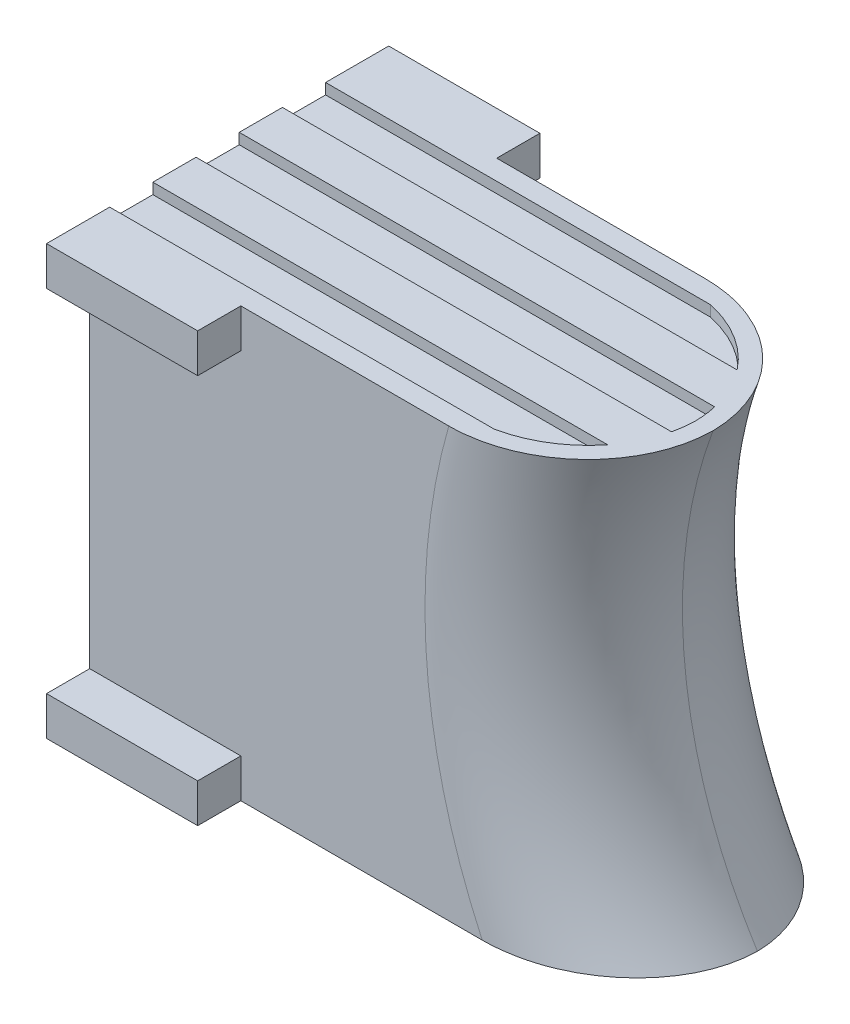
SolidWorks part; units mm, degrees
ref_plane "Front Plane" through (0, 0, 0) normal (0, 0, 1) x (1, 0, 0)
ref_plane "Top Plane" through (0, 0, 0) normal (0, 1, 0) x (1, 0, 0)
ref_plane "Right Plane" through (0, 0, 0) normal (1, 0, 0) x (0, 0, -1)
sketch "Sketch1" plane through (0, 0, 0) normal (0, 0, 1) x (1, 0, 0)
  line L1 (-40, 25.4581) -> (-17.0565, 25.4581)
  line L2 (-40, 25.4581) -> (-40, 5.6081)
  line L3 (-40, 5.6081) -> (-15, 5.6081)
  arc A0 (-17.0565, 25.4581) -> (-15, 5.6081) centre (4, 17.6081) ccw
  dimension "D1" = 19.85
  dimension "D2" = 25
  dimension "D3" = 12
  dimension "D4" = 44
extrude "Boss-Extrude1" add sketch "Sketch1" along normal blind 11.85 contours L1 A0 L3 L2
sketch "Sketch2" plane through (0, 0, 0) normal (0, 0, -1) x (-1, 0, 0)
  line L1 (40, 5.6081) -> (33, 5.6081)
  line L2 (40, 5.6081) -> (40, 7.4081)
  line L3 (40, 7.4081) -> (33, 7.4081)
  line L4 (33, 5.6081) -> (33, 7.4081)
  line L5 (40, 25.4581) -> (33, 25.4581)
  line L6 (40, 25.4581) -> (40, 23.6581)
  line L7 (40, 23.6581) -> (33, 23.6581)
  line L8 (33, 25.4581) -> (33, 23.6581)
  dimension "D1" = 1.8
  dimension "D2" = 7
  dimension "D3" = 1.8
  dimension "D4" = 7
extrude "Boss-Extrude2" add sketch "Sketch2" along normal blind 2 and the other way offset from surface (13.85 mm away) 2 other way up to face at (-28.5952, 15.4729, 11.85)
fillet "Fillet1" radius 6 2 edges at (-18.3526, 15.2923, 0) (-18.3526, 15.2923, 11.85)
sketch "Sketch3" plane through (0, 25.4581, 0) normal (0, 1, 0) x (1, 0, 0)
  line L0 (-40, -13.85) -> (-40, 2) construction
  line L1 (-40, -0.925) -> (-22.1802, -0.925)
  line L2 (-40, -0.925) -> (-40, -2.925)
  line L3 (-40, -2.925) -> (-18.9375, -2.925)
  line L5 (-17.057, -5.925) -> (-46.6866, -5.925) construction
  line L6 (-40, -4.925) -> (-17.9776, -4.925)
  line L7 (-40, -4.925) -> (-40, -6.925)
  line L8 (-40, -6.925) -> (-17.9776, -6.925)
  line L10 (-40, -8.925) -> (-18.9375, -8.925)
  line L11 (-40, -8.925) -> (-40, -10.925)
  line L12 (-40, -10.925) -> (-22.1801, -10.925)
  spline S1 degree 3 poles (-17.9776, -6.925) (-17.9031, -6.5976) (-17.8624, -6.2618) (-17.8571, -5.925) knots 0.878101 0.878101 0.878101 0.878101 1 1 1 1
  spline S2 degree 3 poles (-18.9375, -2.925) (-19.0132, -2.8285) (-19.0925, -2.7343) (-19.2907, -2.5147) (-19.4128, -2.392) (-19.7965, -2.0412) (-20.0767, -1.8299) (-20.6743, -1.4619) (-20.9869, -1.3077) (-21.5913, -1.075) (-21.8839, -0.988) (-22.1802, -0.925) knots 0.393522 0.393522 0.393522 0.393522 0.4375 0.4375 0.5 0.5 0.625 0.625 0.75 0.75 0.857745 0.857745 0.857745 0.857745
  spline S5 degree 3 poles (-4115.5954, 2851.8558) (-146.3035, 359.9865) (-60.4321, -18.0233) (-22.1543, -10.9222) (-21.9847, -10.8827) (-21.6475, -10.7876) (-21.4793, -10.7318) (-20.988, -10.543) (-20.6758, -10.3887) (-20.231, -10.1152) (-20.0871, -10.0174) (-19.8072, -9.807) (-19.6713, -9.6942) (-19.2864, -9.3428) (-19.0548, -9.0868) (-18.6434, -8.5312) (-18.4628, -8.2284) (-18.174, -7.6084) (-18.0615, -7.2852) (-11.3662, 21.4341) (-258.7615, 115.0903) (-1923.6341, -4618.1728) knots -13.76794 -13.76794 -13.76794 -13.76794 0.125 0.125 0.1875 0.1875 0.25 0.25 0.375 0.375 0.4375 0.4375 0.5 0.5 0.625 0.625 0.75 0.75 0.875 0.875 11.458597 11.458597 11.458597 11.458597 only from (-23.3687, -11.05) to (-17.8571, -5.925)
  spline S6 degree 3 poles (-4793.9359, 1430.97) (-471.2744, -182.0611) (-9.0363, -43.6193) (-18.0577, -4.5782) (-18.1717, -4.247) (-18.4619, -3.6228) (-18.6378, -3.3273) (-18.9469, -2.9085) (-19.058, -2.7725) (-19.2907, -2.5147) (-19.4128, -2.392) (-19.7965, -2.0412) (-20.0767, -1.8299) (-20.6743, -1.4619) (-20.9869, -1.3077) (-21.6361, -1.0577) (-21.9779, -0.9607) (-62.8744, 6.6473) (-141.1829, -425.1568) (-4480.5783, -2240.3926) knots -14.470712 -14.470712 -14.470712 -14.470712 0.125 0.125 0.25 0.25 0.375 0.375 0.4375 0.4375 0.5 0.5 0.625 0.625 0.75 0.75 0.875 0.875 15.567897 15.567897 15.567897 15.567897 only from (-17.8571, -5.925) to (-23.3687, -0.8)
  spline S7 degree 3 poles (-22.1801, -10.925) (-22.058, -10.8991) (-21.9368, -10.8692) (-21.6475, -10.7876) (-21.4793, -10.7318) (-20.988, -10.543) (-20.6758, -10.3887) (-20.231, -10.1152) (-20.0871, -10.0174) (-19.8072, -9.807) (-19.6713, -9.6942) (-19.3225, -9.3757) (-19.1205, -9.1584) (-18.9375, -8.925) knots 0.142747 0.142747 0.142747 0.142747 0.1875 0.1875 0.25 0.25 0.375 0.375 0.4375 0.4375 0.5 0.5 0.607411 0.607411 0.607411 0.607411
  spline S8 degree 3 poles (-17.8571, -5.925) (-17.8624, -5.5853) (-17.9032, -5.2516) (-17.9776, -4.925) knots 0 0 0 0 0.123074 0.123074 0.123074 0.123074
  dimension "D1" = 2
  dimension "D2" = 2
  dimension "D3" = 2
  dimension "D4" = 2
  dimension "D5" = 2
  dimension "D7" = 1
  dimension "D6" = 0.8
extrude "Cut-Extrude1" cut sketch "Sketch3" against normal blind 0.5
sketch "Sketch4" plane through (0, 5.6081, 0) normal (0, -1, 0) x (1, 0, 0)
  line L0 (-18.9375, 8.925) -> (-40, 8.925) construction
  line L1 (-40, 10.925) -> (-22.1801, 10.925) construction
  line L2 (-40, 6.925) -> (-17.9776, 6.925) construction
  line L3 (-17.9776, 4.925) -> (-40, 4.925) construction
  line L4 (-40, 2.925) -> (-18.9375, 2.925) construction
  line L5 (-22.1802, 0.925) -> (-40, 0.925) construction
  line L6 (-18.9375, 8.925) -> (-40, 8.925)
  line L7 (-40, 10.925) -> (-22.1801, 10.925)
  line L8 (-40, 6.925) -> (-17.9776, 6.925)
  line L9 (-17.9776, 4.925) -> (-40, 4.925)
  line L10 (-40, 2.925) -> (-18.9375, 2.925)
  line L11 (-22.1802, 0.925) -> (-40, 0.925)
  line L12 (-40, 10.925) -> (-40, 8.925)
  line L13 (-40, 2.925) -> (-40, 0.925)
  line L14 (-40, 6.925) -> (-40, 4.925)
  spline S0 degree 3 poles (-1446.304, -1397.259) (-32.7403, 65.1361) (-10.1083, 12.6893) (-19.2907, 2.5147) (-19.4128, 2.392) (-19.7965, 2.0412) (-20.0767, 1.8299) (-20.6743, 1.4619) (-20.9869, 1.3077) (-38.2068, -5.3244) (-101.7956, 64.1404) (1772.8983, 879.8285) knots -4.683707 -4.683707 -4.683707 -4.683707 0.186233 0.186233 0.248733 0.248733 0.373733 0.373733 0.498733 0.498733 7.004984 7.004984 7.004984 7.004984 only from (-18.9375, 2.925) to (-22.1802, 0.925) construction
  spline S1 degree 3 poles (18.6994, -1989.3681) (-349.9996, 2020.7071) (591.1936, -1940.5262) (-886.0179, 1803.8461) knots -7.795818 -7.795818 -7.795818 -7.795818 7.807574 7.807574 7.807574 7.807574 only from (-17.9776, 6.925) to (-17.8571, 5.925) construction
  spline S2 degree 3 poles (-1963.7948, -436.8831) (1917.4889, 802.1235) (-1773.5354, -1161.2073) (1292.1194, 1499.626) knots -9.441114 -9.441114 -9.441114 -9.441114 14.159845 14.159845 14.159845 14.159845 only from (-17.8571, 5.925) to (-17.9776, 4.925) construction
  spline S3 degree 3 poles (-1997.2069, 306.6523) (-85.3992, -119.3124) (-44.339, 17.183) (-21.6475, 10.7876) (-21.4793, 10.7318) (-20.988, 10.543) (-20.6758, 10.3887) (-20.231, 10.1152) (-20.0871, 10.0174) (-19.8072, 9.807) (-19.6713, 9.6942) (7.4862, -15.1041) (-243.2812, -279.5788) (-1697.5261, -1072.6245) knots -7.913105 -7.913105 -7.913105 -7.913105 0.437342 0.437342 0.499842 0.499842 0.624842 0.624842 0.687342 0.687342 0.749842 0.749842 13.916316 13.916316 13.916316 13.916316 only from (-22.1801, 10.925) to (-18.9375, 8.925) construction
  spline S4 degree 3 poles (-18.9375, 2.925) (-19.0132, 2.8285) (-19.0925, 2.7343) (-19.2907, 2.5147) (-19.4128, 2.392) (-19.7965, 2.0412) (-20.0767, 1.8299) (-20.6743, 1.4619) (-20.9869, 1.3077) (-21.5913, 1.075) (-21.8839, 0.988) (-22.1802, 0.925) knots 0.142255 0.142255 0.142255 0.142255 0.186233 0.186233 0.248733 0.248733 0.373733 0.373733 0.498733 0.498733 0.606478 0.606478 0.606478 0.606478
  spline S5 degree 3 poles (-17.9776, 6.925) (-17.9031, 6.5976) (-17.8624, 6.2618) (-17.8571, 5.925) knots 0 0 0 0 0.121899 0.121899 0.121899 0.121899
  spline S6 degree 3 poles (-17.8571, 5.925) (-17.8624, 5.5853) (-17.9032, 5.2516) (-17.9776, 4.925) knots 0.876926 0.876926 0.876926 0.876926 1 1 1 1
  spline S7 degree 3 poles (-22.1801, 10.925) (-22.058, 10.8991) (-21.9368, 10.8692) (-21.6475, 10.7876) (-21.4793, 10.7318) (-20.988, 10.543) (-20.6758, 10.3887) (-20.231, 10.1152) (-20.0871, 10.0174) (-19.8072, 9.807) (-19.6713, 9.6942) (-19.3225, 9.3757) (-19.1205, 9.1584) (-18.9375, 8.925) knots 0.392589 0.392589 0.392589 0.392589 0.437342 0.437342 0.499842 0.499842 0.624842 0.624842 0.687342 0.687342 0.749842 0.749842 0.857253 0.857253 0.857253 0.857253
extrude "Cut-Extrude2" cut sketch "Sketch4" against normal blind 0.5
sketch "Sketch6" plane through (-40, 0, 0) normal (-1, 0, 0) x (0, 0, 1)
  line L2 (0, 23.6581) -> (0, 7.4081) construction
  line L3 (0.925, 25.4581) -> (-2, 25.4581) construction
  circle A0 centre (2.85, 15.4581) radius 2.65
  circle A1 centre (2.85, 15.4581) radius 1.5
  dimension "D1" = 5.3
  dimension "D2" = 3
  dimension "D3" = 2.85
  dimension "D4" = 10
extrude "Cut-Extrude3" cut sketch "Sketch6" against normal blind 10
